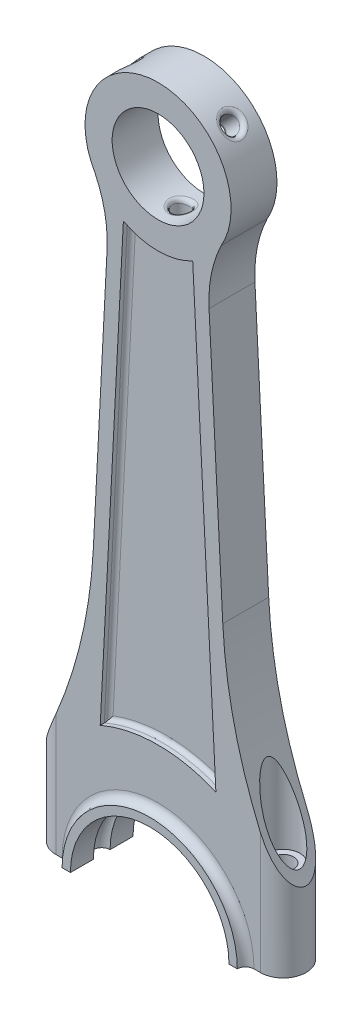
SolidWorks part; units mm, degrees
ref_plane "Front Plane" through (0, 0, 0) normal (0, 0, 1) x (1, 0, 0)
ref_plane "Top Plane" through (0, 0, 0) normal (0, 1, 0) x (1, 0, 0)
ref_plane "Right Plane" through (0, 0, 0) normal (1, 0, 0) x (0, 0, -1)
sketch "Sketch1" plane through (0, 0, 0) normal (0, 0, 1) x (1, 0, 0)
  line L0 (0, 0) -> (0, 155) construction
  line L1 (0, 0) -> (90.3578, 0) construction
  line L2 (12.2196, 131.6851) -> (15.5154, 67.9144)
  line L3 (30, 18) -> (30, 0)
  line L4 (30, 0) -> (19, 0)
  line L5 (-30, 18) -> (-30, 0)
  line L6 (-30, 0) -> (-19, 0)
  line L7 (-12.2196, 131.6851) -> (-15.5154, 67.9144)
  circle A0 centre (0, 155) radius 11
  arc A1 (15.1271, 146.2011) -> (-15.1271, 146.2011) centre (0, 155) ccw
  circle A2 centre (0, 0) radius 34.9857 construction
  arc A3 (19, 0) -> (-19, 0) centre (0, 0) ccw
  arc A4 (15.5154, 67.9144) -> (30, 18) centre (128.9667, 73.7778) ccw
  arc A5 (12.2196, 131.6851) -> (15.1271, 146.2011) centre (42.1797, 133.2335) cw
  arc A6 (-15.5154, 67.9144) -> (-30, 18) centre (-128.9667, 73.7778) cw
  arc A7 (-12.2196, 131.6851) -> (-15.1271, 146.2011) centre (-42.1797, 133.2335) ccw
  dimension "D1" = 38
  dimension "D2" = 22
  dimension "D3" = 35
  dimension "D7" = 30
  dimension "D4" = 155
  dimension "D5" = 18
  dimension "D6" = 30
extrude "Boss-Extrude1" add sketch "Sketch1" along normal mid plane 11
sketch "Sketch2" plane through (0, 0, 5.5) normal (0, 0, 1) x (1, 0, 0)
  line L0 (8.3061, 139.5968) -> (13.8597, 32.1389)
  line L1 (15.5154, 67.9144) -> (12.2196, 131.6851) construction
  line L2 (0, 155) -> (0, 0) construction
  line L3 (-8.3061, 139.5968) -> (-13.8597, 32.1389)
  arc A0 (-8.3061, 139.5968) -> (8.3061, 139.5968) centre (0, 155) ccw
  arc A1 (13.8597, 32.1389) -> (-13.8597, 32.1389) centre (0, 0) ccw
  dimension "D1" = 35
  dimension "D2" = 70
  dimension "D3" = 3.5
extrude "Cut-Extrude1" cut sketch "Sketch2" against normal blind 2
sketch "Sketch4" plane through (0, 0, 0) normal (0, -1, 0) x (1, 0, 0)
  line L0 (-30, 0) -> (-19, 0) construction
  line L1 (-30, 5.5) -> (-30, -5.5) construction
  line L2 (-19, 5.5) -> (-19, -5.5) construction
  line L4 (19, 5.5) -> (19, -5.5) construction
  line L5 (19, 0) -> (30, 0) construction
  line L6 (30, 5.5) -> (30, -5.5) construction
  circle A0 centre (-24.5, 0) radius 2.5
  circle A1 centre (24.5, 0) radius 2.5
  dimension "D1" = 5
  dimension "D2" = 5
extrude "Cut-Extrude2" cut sketch "Sketch4" against normal through all
sketch "Sketch5" plane through (0, 0, 0) normal (0, -1, 0) x (1, 0, 0)
  circle A0 centre (-24.5, 0) radius 4
  circle A1 centre (24.5, 0) radius 4
  dimension "D1" = 8
  dimension "D2" = 8
extrude "Cut-Extrude3" cut sketch "Sketch5" against normal through all from offset 20 offset against normal yes
sketch "Sketch6" plane through (0, 0, 5.5) normal (0, 0, 1) x (1, 0, 0)
  line L0 (-21, 0) -> (-19, 0)
  line L1 (19, 0) -> (21, 0)
  circle A0 centre (0, 0) radius 19
  circle A1 centre (0, 0) radius 21
  line M13 (-30, 0) -> (-19, 0)
  arc M14 (-19, 0) -> (19, 0) centre (0, 0) cw
  line M15 (19, 0) -> (30, 0)
  dimension "D1" = 42
extrude "Boss-Extrude2" add sketch "Sketch6" along normal blind 2 contours A1 M15 M13 M14 region at (0, 20.5304, 5.5)
mirror "Mirror1" about plane through (0, 0, 0) normal (0, 0, 1) of "Cut-Extrude1", "Boss-Extrude2"
sketch "Sketch7" plane through (0, 0, 0) normal (0, -1, 0) x (1, 0, 0)
  line L0 (19, 7.5) -> (19, -7.5) construction
  line L1 (0, 0) -> (0, -10.329) construction
  circle A0 centre (19, 0) radius 2
  dimension "D1" = 4
revolve "Cut-Revolve1" cut sketch "Sketch7" angle 360 about L1
sketch "Sketch8" plane through (0, 0, 0) normal (0, -1, 0) x (1, 0, 0)
  circle A0 centre (0, 0) radius 2
  dimension "D1" = 4
extrude "Cut-Extrude4" cut sketch "Sketch8" against normal up to next
sketch "Sketch9" plane through (0, 0, 0) normal (0, 0, 1) x (1, 0, 0)
  line L0 (0, 172.5) -> (0, 155) construction
  line L1 (0, 155) -> (-16.4376, 171.4376)
  arc A0 (15.1271, 146.2011) -> (-15.1271, 146.2011) centre (0, 155) ccw construction
  dimension "D1" = 45
sweep "Cut-Sweep1" cut path "Sketch9" circular profile diameter 4 parameters "D3"=4
mirror "Mirror2" about plane through (0, 0, 0) normal (1, 0, 0) of "Cut-Sweep1"
fillet "Fillet1" 2 edges at (-30, 9, -5.5) (-30, 9, 5.5) type full round first side face at (0, 64.4655, -5.5) second side face at (0, 64.4655, 5.5) middle face at (-30, 9, 0)
fillet "Fillet2" 2 edges at (30, 9, -5.5) (30, 9, 5.5) type full round first side face at (0.8182, 65.4309, -5.5) second side face at (0.8182, 65.4309, 5.5) middle face at (30, 9, 0)
fillet "Fillet3" radius 2 2 edges at (0, 21, 5.5) (0, 21, -5.5)
fillet "Fillet4" radius 1 15 edges at (11.0829, 85.8678, 3.5) (0, 35, 3.5) (-11.0829, 85.8678, 3.5) (0, 137.5, 3.5) (-11.0829, 85.8678, -3.5) (0, 35, -3.5) (11.0829, 85.8678, -3.5) (0, 137.5, -3.5) (-10.9186, 168.676, 0.4454) (-6.2722, 164.0366, 0.4233) (-1.9927, 20.8979, 0.1708) (1.9927, 20.8979, -0.1708) (-0.4232, 144.0081, 1.9547) (13.676, 165.9186, 0.4454) (9.0366, 161.2722, 0.4233)
